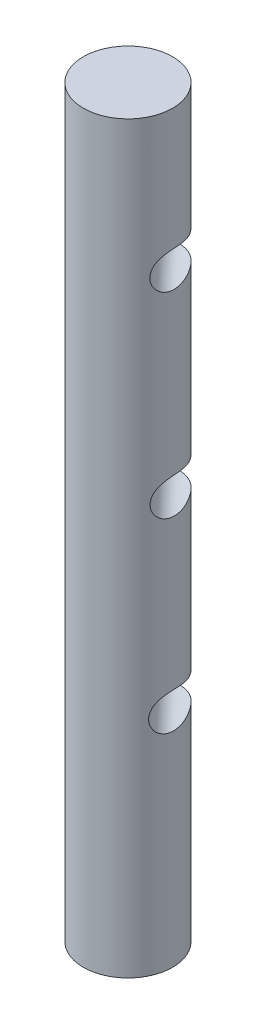
SolidWorks part; units mm, degrees
ref_plane "Front Plane" through (0, 0, 0) normal (0, 0, 1) x (1, 0, 0)
ref_plane "Top Plane" through (0, 0, 0) normal (0, 1, 0) x (1, 0, 0)
ref_plane "Right Plane" through (0, 0, 0) normal (1, 0, 0) x (0, 0, -1)
sketch "Sketch1" plane through (0, 0, 0) normal (0, 1, 0) x (1, 0, 0)
  circle A0 centre (0, 0) radius 7.5
extrude "Boss-Extrude1" add sketch "Sketch1" along normal blind 125
hole_wizard "Ø6.0mm Dowel Hole1" positions "Sketch2" profile "Sketch3" hole size "Ø6.0" standard "ANSI Metric" end condition through all
sketch "Sketch2" plane through (63.1327, -54.5795, -196.6841) normal (-0.6877, 0, -0.726) x (0, 1, 0)
  point P0 (156.0875, -175.3187)
sketch "Sketch3" plane through (-64.1418, 101.5081, -76.1111) normal (0, 1, 0) x (-0.726, 0, 0.6877)
  line L0 (0, 0) -> (0, 109.9691)
  line L1 (0, 109.9691) -> (3, 109.9691)
  line L2 (3, 109.9691) -> (3, 0)
  line L3 (3, 0) -> (0, 0)
  line L4 (0, -6.35) -> (0, 107.95) construction
  dimension "Thru Hole Dia." = 6
  dimension "Thru Hole Depth" = 109.9691
hole_wizard "Ø6.0mm Dowel Hole2" positions "Sketch4" profile "Sketch5" hole size "Ø6.0" standard "ANSI Metric" end condition through all
sketch "Sketch4" plane through (63.1327, -54.5795, -196.6841) normal (-0.6877, 0, -0.726) x (0, 1, 0)
  point P0 (123.0979, -175.281)
sketch "Sketch5" plane through (-64.1145, 68.5184, -76.1371) normal (0, 1, 0) x (-0.726, 0, 0.6877)
  line L0 (0, 0) -> (0, 109.9691)
  line L1 (0, 109.9691) -> (3, 109.9691)
  line L2 (3, 109.9691) -> (3, 0)
  line L3 (3, 0) -> (0, 0)
  line L4 (0, -6.35) -> (0, 107.95) construction
  dimension "Thru Hole Dia." = 6
  dimension "Thru Hole Depth" = 109.9691
hole_wizard "Ø6.0mm Dowel Hole4" positions "Sketch8" profile "Sketch9" hole size "Ø6.0" standard "ANSI Metric" end condition through all
sketch "Sketch8" plane through (63.1327, -54.5795, -196.6841) normal (-0.6877, 0, -0.726) x (0, 1, 0)
  point P0 (91.9018, -175.4545)
sketch "Sketch9" plane through (-64.2404, 37.3224, -76.0178) normal (0, 1, 0) x (-0.726, 0, 0.6877)
  line L0 (0, 0) -> (0, 109.9691)
  line L1 (0, 109.9691) -> (3, 109.9691)
  line L2 (3, 109.9691) -> (3, 0)
  line L3 (3, 0) -> (0, 0)
  line L4 (0, -6.35) -> (0, 107.95) construction
  dimension "Thru Hole Dia." = 6
  dimension "Thru Hole Depth" = 109.9691
